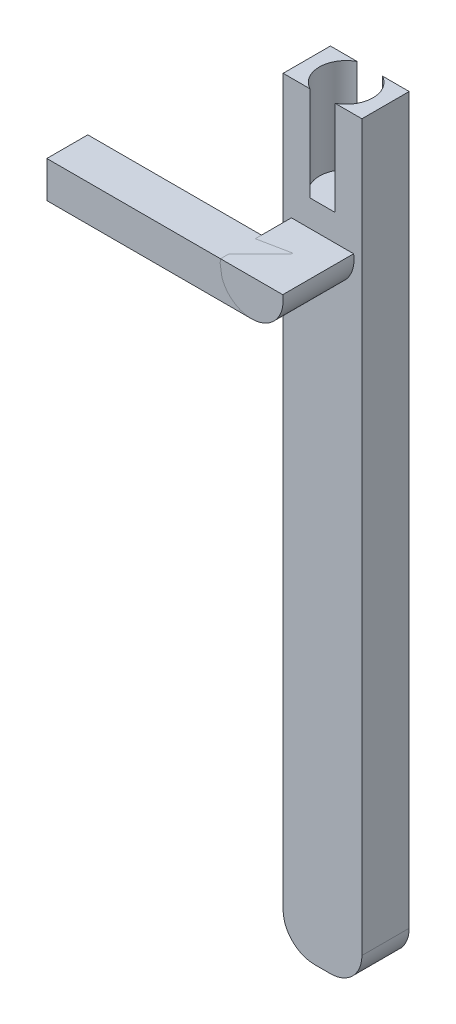
SolidWorks part; units mm, degrees
ref_plane "Спереди" through (0, 0, 0) normal (0, 0, 1) x (1, 0, 0)
ref_plane "Сверху" through (0, 0, 0) normal (0, 1, 0) x (1, 0, 0)
ref_plane "Справа" through (0, 0, 0) normal (1, 0, 0) x (0, 0, -1)
sketch "Эскиз1" plane through (0, 0, 0) normal (0, 0, 1) x (1, 0, 0)
  line L1 (-1, 0) -> (-1.5, 0)
  line L2 (0, 1) -> (0, 24)
  line L3 (0, 24) -> (-2.5, 24)
  line L4 (-2.5, 1) -> (-2.5, 24)
  arc A0 (-1, 0) -> (0, 1) centre (-1, 1) ccw
  arc A1 (-1.5, 0) -> (-2.5, 1) centre (-1.5, 1) cw
  point P7 (0, 0)
  point P10 (-2.5, 0)
  dimension "D3" = 1
  dimension "D1" = 24
  dimension "D2" = 2.5
extrude "Бобышка-Вытянуть1" add sketch "Эскиз1" along normal blind 1.5
sketch "Эскиз2" plane through (0, 0, 1.5) normal (0, 0, 1) x (1, 0, 0)
  line L0 (-1.25, 24) -> (-1.25, 20) construction
  line L1 (0, 24) -> (-2.5, 24) construction
  circle A0 centre (-1.25, 20) radius 1
  dimension "D2" = 2
  dimension "D1" = 4
extrude "Бобышка-Вытянуть2" add sketch "Эскиз2" along normal blind 2.25
sketch "Эскиз3" plane through (0, 24, 0) normal (0, 1, 0) x (1, 0, 0)
  line L0 (-2.5, -1.5) -> (0, 0) construction
  circle A0 centre (-1.25, -0.75) radius 0.85
  dimension "D1" = 1.7
extrude "Вырез-Вытянуть1" cut sketch "Эскиз3" against normal blind 3
ref_plane "Плоскость1" through (0, 19, 0) normal (0, -1, 0) x (-1, 0, 0)
sketch "Эскиз4" plane through (0, 19, 0) normal (0, -1, 0) x (-1, 0, 0)
  line L0 (2.25, -3.75) -> (2.25, -1.5) construction
  line L1 (2.25, -3.75) -> (7.75, -3.75)
  line L3 (2.25, -2.45) -> (7.75, -2.45)
  line L4 (7.75, -3.75) -> (7.75, -2.45)
  line L5 (0.25, -3.75) -> (2.25, -3.75) construction
  line L6 (2.25, -2.45) -> (1.25, -2.45)
  line L8 (2.25, -3.75) -> (1.25, -3.75)
  line L9 (1.25, -2.45) -> (1.25, -3.75)
  dimension "D1" = 1.3
  dimension "D2" = 5.5
extrude "Бобышка-Вытянуть3" add sketch "Эскиз4" against normal blind 2 separate body
sketch "Эскиз5" plane through (0, 0, 3.75) normal (0, 0, 1) x (1, 0, 0)
  line L1 (-7.75, 21) -> (0.4357, 21)
  line L2 (-7.75, 21) -> (-7.75, 20.1585)
  line L3 (-7.75, 20.1585) -> (0.4357, 20.1585)
  line L4 (0.4357, 21) -> (0.4357, 20.1585)
extrude "Вырез-Вытянуть2" cut sketch "Эскиз5" against normal up to surface (2.25 mm away) up to face at (-1.1667, 15.0488, 1.5)
